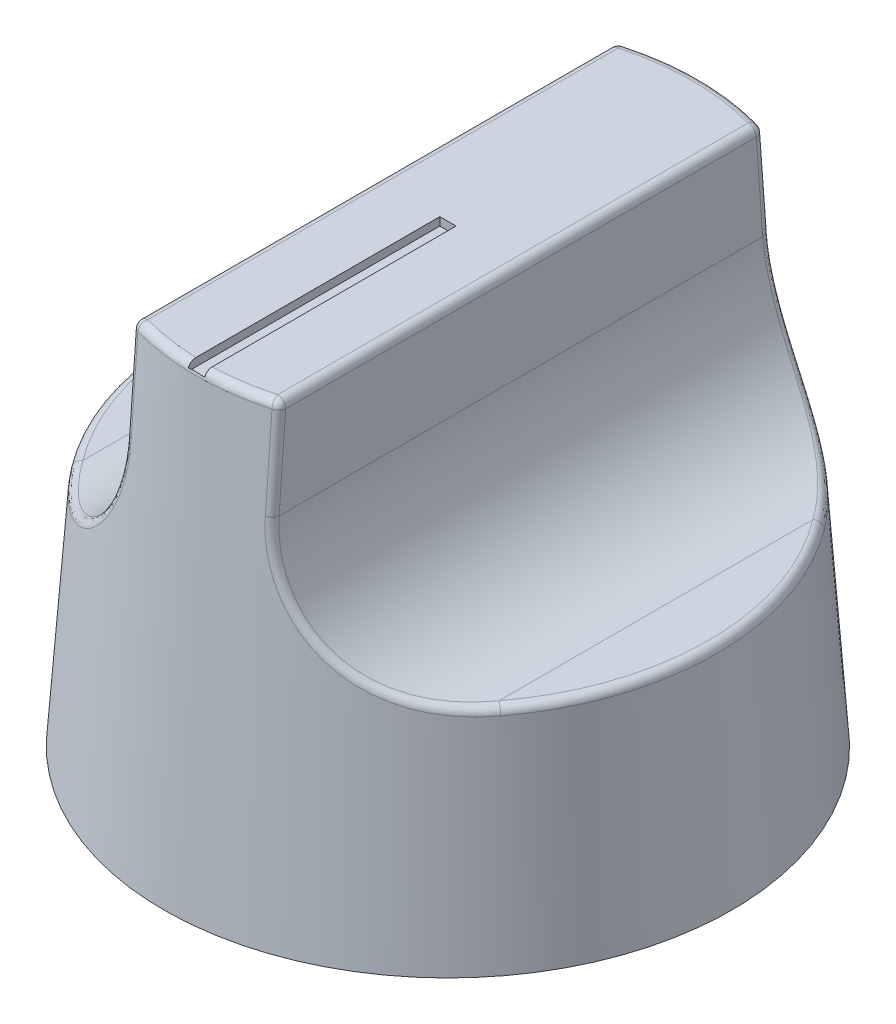
SolidWorks part; units mm, degrees
ref_plane "Plan de face" through (0, 0, 0) normal (0, 0, 1) x (1, 0, 0)
ref_plane "Plan de dessus" through (0, 0, 0) normal (0, 1, 0) x (1, 0, 0)
ref_plane "Plan de droite" through (0, 0, 0) normal (1, 0, 0) x (0, 0, -1)
sketch "Esquisse1" plane through (0, 0, 0) normal (0, 0, 1) x (1, 0, 0)
  line L0 (0, 0) -> (-17.5, 0)
  line L1 (-17.5, 0) -> (-15.5, 28)
  line L2 (-15.5, 28) -> (0, 28)
  line L3 (0, 28) -> (0, 0)
  dimension "D1" = 15.5
  dimension "D2" = 17.5
  dimension "D3" = 28
revolve "Révolution1" add sketch "Esquisse1" angle 360 about L3
sketch "Esquisse2" plane through (0, 0, 0) normal (0, 0, 1) x (1, 0, 0)
  line L0 (0, 0) -> (0, 28) construction
  line L1 (15.5, 28) -> (-15.5, 28) construction
  line L2 (0, 28) -> (0, 0) construction
ref_plane "Plan1" through (0, 0, 10) normal (0, 0, 1) x (1, 0, 0)
sketch "Esquisse4" plane through (0, 0, 0) normal (0, -1, 0) x (1, 0, 0)
  line L0 (3.257, 0.9758) -> (-1.5139, 3.0443)
  arc A1 (-1.5139, 3.0443) -> (3.257, 0.9758) centre (0, 0) ccw
  dimension "D1" = 5.2
  dimension "D2" = 3.4
extrude "Enlèv. mat.-Extru.2" cut sketch "Esquisse4" against normal blind 23 draft 0.5
ref_plane "Plan2" through (0, 20, 0) normal (0, 1, 0) x (1, 0, 0)
ref_plane "Plan3" through (0, -10, 0) normal (0, -1, 0) x (-1, 0, 0)
sketch "Esquisse5" plane through (0, -10, 0) normal (0, -1, 0) x (-1, 0, 0)
  circle A0 centre (0, 0) radius 5.5
  circle A1 centre (0, 0) radius 15.25
  dimension "D1" = 30.5
  dimension "D2" = 11
extrude "Enlèv. mat.-Extru.3" cut sketch "Esquisse5" against normal blind 22 draft 3
sketch "Esquisse6" plane through (0, -10, 0) normal (0, -1, 0) x (-1, 0, 0)
  circle A0 centre (0, 0) radius 7.9745
extrude "Enlèv. mat.-Extru.4" cut sketch "Esquisse6" against normal blind 11
ref_plane "Plan4" through (0, 0, 20) normal (0, 0, -1) x (-1, 0, 0)
sketch "Esquisse7" plane through (0, 0, 20) normal (0, 0, -1) x (-1, 0, 0)
  line L0 (18.8204, 13.6663) -> (12.8204, 13.6663)
  line L1 (4.5, 28) -> (4.5, 21.9867)
  line L2 (15.5, 28) -> (-15.5, 28) construction
  line L3 (4.5, 28) -> (18.8204, 28)
  line L4 (18.8204, 28) -> (18.8204, 13.6663)
  arc A0 (12.8204, 13.6663) -> (4.5, 21.9867) centre (12.8204, 21.9867) cw
  dimension "D2" = 4.5
  dimension "D1" = 6
extrude "Enlèv. mat.-Extru.6" cut sketch "Esquisse7" along normal through all
mirror "Symétrie1" about plane through (0, 0, 0) normal (1, 0, 0) of "Enlèv. mat.-Extru.6"
fillet "Congé1" radius 0.5 14 edges at (16.5238, 13.6663, 0) (-7.8546, 15.3106, 14.404) (7.8546, 15.3106, 14.404) (6.3439, 16.7633, -15.0177) (-6.3439, 16.7633, -15.0177) (-16.5238, 13.6663, 0) (0, 28, -15.5) (4.5, 28, 0) (-4.5, 28, 0) (0, 28, 15.5)
ref_plane "Plan5" through (0, 38, 0) normal (0, 1, 0) x (1, 0, 0)
sketch "Esquisse8" plane through (0, 38, 0) normal (0, 1, 0) x (1, 0, 0)
  line L0 (0.5, -15.4919) -> (0.5, 0)
  line L2 (0.5, 0) -> (-0.5, 0)
  line L3 (-0.5, -15.4919) -> (-0.5, 0)
  line L4 (0.5, -15.4919) -> (-0.5, 0) construction
  line L5 (0.5, 0) -> (-0.5, -15.4919) construction
  line L7 (-0.5, -15.4919) -> (0.5, -15.4919)
  arc A0 (-4, -14.975) -> (4, -14.975) centre (0, 0) ccw construction
  point P1 (0, -5)
  dimension "D1" = 1
extrude "Enlèv. mat.-Extru.7" cut sketch "Esquisse8" against normal blind 10.5
fillet "Congé2" radius 5 1 edges at (6.653, 12, 0)
